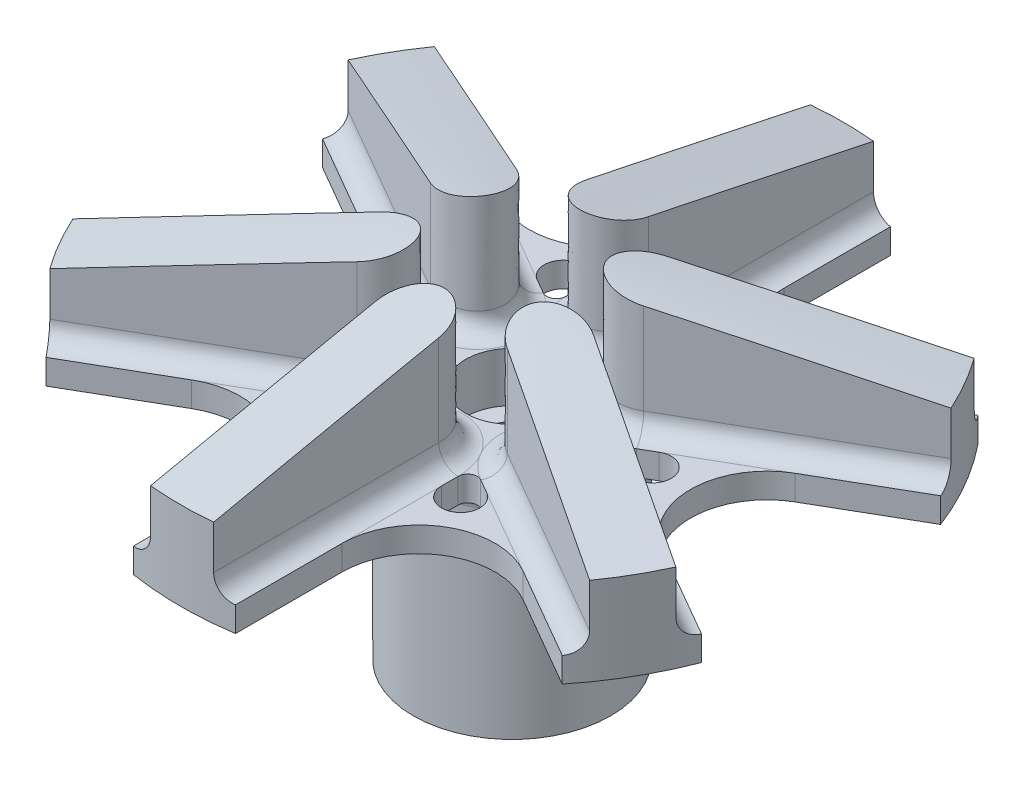
SolidWorks part; units mm, degrees
ref_plane "Front Plane" through (0, 0, 0) normal (0, 0, 1) x (1, 0, 0)
ref_plane "Top Plane" through (0, 0, 0) normal (0, 1, 0) x (1, 0, 0)
ref_plane "Right Plane" through (0, 0, 0) normal (1, 0, 0) x (0, 0, -1)
sketch "Sketch1" plane through (0, 0, 0) normal (0, 1, 0) x (1, 0, 0)
  circle A0 centre (0, 0) radius 26.67
  dimension "D1" = 53.34
extrude "impeller plate" add sketch "Sketch1" along normal blind 2
sketch "Sketch6" plane through (0, 0, 0) normal (0, -1, 0) x (-1, 0, 0)
  circle A0 centre (0, 0) radius 7.9375
  dimension "D1" = 15.875
extrude "boss" add sketch "Sketch6" along normal blind 17
sketch "Sketch7" plane through (0, -17, 0) normal (0, -1, 0) x (-1, 0, 0)
  circle A0 centre (0, 0) radius 2.1828
  dimension "D1" = 4.3656
extrude "bolt bore" cut sketch "Sketch7" against normal through all
sketch "Sketch8" plane through (0, -17, 0) normal (0, -1, 0) x (-1, 0, 0)
  circle A0 centre (0, 0) radius 4
  dimension "D1" = 8
extrude "shaft bore" cut sketch "Sketch8" against normal blind 12
sketch "Sketch9" plane through (0, 2, 0) normal (0, 1, 0) x (1, 0, 0)
  circle A0 centre (0, 0) radius 3.75
  dimension "D1" = 7.5
extrude "bolt head bore" cut sketch "Sketch9" against normal blind 4
sketch "Sketch11" plane through (0, -17, 0) normal (0, -1, 0) x (1, 0, 0)
  line L1 (-6, 1) -> (6, 1)
  line L2 (-6, 1) -> (-6, -1)
  line L3 (-6, -1) -> (6, -1)
  line L4 (6, 1) -> (6, -1)
  line L5 (-6, 1) -> (6, -1) construction
  line L6 (-6, -1) -> (6, 1) construction
  point P0 (0, 0)
  dimension "D1" = 12
  dimension "D2" = 2
extrude "dowel slot" cut sketch "Sketch11" against normal blind 3
sketch "Sketch12" plane through (0, 2, 0) normal (0, 1, 0) x (1, 0, 0)
  line L0 (0, 0) -> (26.67, 0) construction
  line L1 (5.2327, 1.5626) -> (26.6242, 1.5626)
  line L2 (5.2327, -1.5626) -> (26.6242, -1.5626)
  circle A0 centre (0, 0) radius 26.67 construction
  arc A3 (26.6242, -1.5626) -> (26.6242, 1.5626) centre (0, 0) ccw
  arc A4 (5.2327, -1.5626) -> (5.2327, 1.5626) centre (0, 0) ccw
  dimension "D3" = 10.922
  dimension "D1" = 1.5626
  dimension "D2" = 1.5626
extrude "opening alingment cut" cut sketch "Sketch12" against normal blind 1
pattern_circular "opening alingment pattern" count 6 over 360 about axis through (0, 2, 0) along (0, 1, 0) of "opening alingment cut"
sketch "Sketch14" plane through (0, 2, 0) normal (0, 1, 0) x (1, 0, 0)
  line L0 (0, 0) -> (26.67, 0) construction
  line L1 (26.6242, 1.5626) -> (5.2327, 1.5626) construction
  line L3 (24.2619, 11.0747) -> (8.5761, 2.0185) construction
  line L5 (0, 0) -> (23.0969, 13.335) construction
  line L7 (6.0361, 6.4179) -> (21.7219, 15.4741)
  line L9 (8.5761, 2.0185) -> (24.2619, 11.0747)
  arc A2 (26.6242, -1.5626) -> (26.6242, 1.5626) centre (0, 0) ccw construction
  arc A5 (26.6242, 1.5626) -> (14.6654, 22.2759) centre (0, 0) ccw construction
  circle A6 centre (0, 0) radius 5.461 construction
  circle A7 centre (0, 0) radius 5.461 construction
  arc A8 (24.2619, 11.0747) -> (21.7219, 15.4741) centre (0, 0) ccw
  ellipse E0 centre (7.3061, 4.2182) end of major axis (4.7294, 2.7305) minor radius 2.54 (6.0361, 6.4179) -> (8.5761, 2.0185) ccw
  dimension "D1" = 30
  dimension "D2" = 5.08
extrude "one blade" add sketch "Sketch14" along normal blind 9.5881
sketch "Sketch15" plane through (0, 2, 0) normal (0, 1, 0) x (1, 0, 0)
  circle A0 centre (0, 0) radius 26.67
  arc A1 (-26.6242, -1.5626) -> (-14.6654, -22.2759) centre (0, 0) ccw construction
  circle A2 centre (0, 0) radius 3.75
  circle A3 centre (0, 0) radius 3.75 construction
extrude "opening alignment fill" add sketch "Sketch15" against normal blind 2
pattern_circular "CirPattern2" count 6 over 360 about axis through (0, 2, 0) along (0, 1, 0) of "one blade"
sketch "Sketch16" plane through (0, 0, 0) normal (1, 0, 0) x (0, 0, -1)
  line L0 (0, 0) -> (0, 11.5881) construction
  line L2 (26.67, 0) -> (26.67, 7.08) construction
  line L3 (0, 11.5881) -> (5.461, 11.5881) construction
  line L4 (5.461, 11.5881) -> (26.67, 7.08)
  line L5 (26.67, 7.08) -> (26.67, 11.5881)
  line L6 (26.67, 11.5881) -> (5.461, 11.5881)
  line L7 (-26.67, 0) -> (26.67, 0) construction
  dimension "D1" = 7.08
  dimension "D2" = 5.461
  dimension "D3" = 26.67
  dimension "D4" = 11.5881
revolve "angle cut" cut sketch "Sketch16" angle 360 about L0
fillet "Fillet1" radius 1.5626 18 edges at (-16.419, 2, -6.5466) (-4.7294, 2, -2.7305) (-2.54, 2, -17.4926) (0, 2, -5.461) (16.419, 2, -6.5466) (4.7294, 2, -2.7305) (13.879, 2, 10.946) (4.7294, 2, 2.7305) (-13.879, 2, 10.946) (-16.419, 2, 6.5466) (-2.54, 2, 17.4926) (0, 2, 5.461) (-13.879, 2, -10.946) (2.54, 2, -17.4926) (13.879, 2, -10.946) (16.419, 2, 6.5466) (-4.7294, 2, 2.7305) (2.54, 2, 17.4926)
sketch "Sketch18" plane through (0, 2, 0) normal (0, 1, 0) x (1, 0, 0)
  line L0 (-20.7707, -16.7293) -> (-13.335, -12.4363)
  line L1 (4.1026, -26.3526) -> (4.1026, -17.7666)
  line L2 (4.1026, -8.4364) -> (4.1026, -26.3526) construction
  line L3 (20.7707, -16.7293) -> (13.335, -12.4363)
  line L4 (20.7707, -16.7293) -> (5.2548, -7.7712) construction
  line L5 (-4.1026, -26.3526) -> (-4.1026, -17.7666)
  line L6 (-24.8733, 9.6233) -> (-17.4376, 5.3303)
  line L7 (-24.8733, -9.6233) -> (-17.4376, -5.3303)
  line L8 (-4.1026, 26.3526) -> (-4.1026, 17.7666)
  line L9 (-20.7707, 16.7293) -> (-13.335, 12.4363)
  line L10 (20.7707, 16.7293) -> (13.335, 12.4363)
  line L11 (4.1026, 26.3526) -> (4.1026, 17.7666)
  line L12 (24.8733, -9.6233) -> (17.4376, -5.3303)
  line L13 (24.8733, 9.6233) -> (17.4376, 5.3303)
  line L14 (5.6414, -9.7711) -> (7.1801, -12.4363) construction
  line L15 (5.2548, -7.7712) -> (6.4107, -8.4386)
  line L16 (4.1026, -8.4364) -> (4.1026, -9.7711)
  line L17 (-4.1026, -8.4364) -> (-4.1026, -9.7711)
  line L18 (-5.2548, -7.7712) -> (-6.4107, -8.4386)
  line L19 (-9.3575, -0.6652) -> (-10.5134, -1.3326)
  line L20 (-9.3575, 0.6652) -> (-10.5134, 1.3326)
  line L21 (-5.2548, 7.7712) -> (-6.4107, 8.4386)
  line L22 (-4.1026, 8.4364) -> (-4.1026, 9.7711)
  line L23 (4.1026, 8.4364) -> (4.1026, 9.7711)
  line L24 (5.2548, 7.7712) -> (6.4107, 8.4386)
  line L25 (9.3575, 0.6652) -> (10.5134, 1.3326)
  line L26 (9.3575, -0.6652) -> (10.5134, -1.3326)
  arc A0 (4.1026, -17.7666) -> (13.335, -12.4363) centre (10.2575, -17.7666) cw
  arc A1 (4.1026, -26.3526) -> (20.7707, -16.7293) centre (0, 0) ccw
  circle A2 centre (10.2575, -17.7666) radius 6.1549 construction
  arc A3 (-20.7707, -16.7293) -> (-4.1026, -26.3526) centre (0, 0) ccw
  arc A4 (-13.335, -12.4363) -> (-4.1026, -17.7666) centre (-10.2575, -17.7666) cw
  arc A5 (-24.8733, 9.6233) -> (-24.8733, -9.6233) centre (0, 0) ccw
  arc A6 (-17.4376, 5.3303) -> (-17.4376, -5.3303) centre (-20.5151, 0) cw
  arc A7 (-4.1026, 26.3526) -> (-20.7707, 16.7293) centre (0, 0) ccw
  arc A8 (-4.1026, 17.7666) -> (-13.335, 12.4363) centre (-10.2575, 17.7666) cw
  arc A9 (20.7707, 16.7293) -> (4.1026, 26.3526) centre (0, 0) ccw
  arc A10 (13.335, 12.4363) -> (4.1026, 17.7666) centre (10.2575, 17.7666) cw
  arc A11 (24.8733, -9.6233) -> (24.8733, 9.6233) centre (0, 0) ccw
  arc A12 (17.4376, -5.3303) -> (17.4376, 5.3303) centre (20.5151, 0) cw
  arc A13 (4.1026, -9.7711) -> (6.4107, -8.4386) centre (5.6414, -9.7711) ccw
  arc A14 (5.2548, -7.7712) -> (4.1026, -8.4364) centre (4.8708, -8.4364) ccw
  arc A15 (-6.4107, -8.4386) -> (-4.1026, -9.7711) centre (-5.6414, -9.7711) ccw
  arc A16 (-4.1026, -8.4364) -> (-5.2548, -7.7712) centre (-4.8708, -8.4364) ccw
  arc A17 (-10.5134, 1.3326) -> (-10.5134, -1.3326) centre (-11.2827, 0) ccw
  arc A18 (-9.3575, -0.6652) -> (-9.3575, 0.6652) centre (-9.7415, 0) ccw
  arc A19 (-4.1026, 9.7711) -> (-6.4107, 8.4386) centre (-5.6414, 9.7711) ccw
  arc A20 (-5.2548, 7.7712) -> (-4.1026, 8.4364) centre (-4.8708, 8.4364) ccw
  arc A21 (6.4107, 8.4386) -> (4.1026, 9.7711) centre (5.6414, 9.7711) ccw
  arc A22 (4.1026, 8.4364) -> (5.2548, 7.7712) centre (4.8708, 8.4364) ccw
  arc A23 (10.5134, -1.3326) -> (10.5134, 1.3326) centre (11.2827, 0) ccw
  arc A24 (9.3575, 0.6652) -> (9.3575, -0.6652) centre (9.7415, 0) ccw
  spline S0 degree 3 poles (5.2548, -7.7712) (4.8829, -7.5565) (4.54, -7.295) (3.9364, -6.6984) (3.6698, -6.3563) (3.4573, -5.9882) knots 0 0 0 0 0.5 0.5 1 1 1 1 construction
  spline S1 degree 3 poles (3.4573, -5.9882) (3.5634, -6.1719) (3.6568, -6.3628) (3.8185, -6.7587) (3.8868, -6.9643) (4.0486, -7.5836) (4.1026, -8.0054) (4.1026, -8.4364) knots 0 0 0 0 0.25 0.25 0.5 0.5 1 1 1 1 construction
  point P16 (6.4107, -11.1037)
  point P85 (0, 0)
  dimension "D1" = 6
extrude "Cut-Extrude1" cut sketch "Sketch18" against normal through all
fillet "Fillet3" radius 1.016 1 edges at (0, 0, 7.9375)
equation "\"z\" = 6\t\t\t'number of blades"
equation "\"de_length\" = 10mm\t\t'entrance eye consistent length"
equation "\"av\" = \"ae\"*\"av_ratio\"\t\t'area between just two blades"
equation "\"d2\" = 2.1in \t\t\t'outer diameter of the impeller"
equation "\"theta\" = 12\t\t\t'angle of blades from inner to outer "
equation "\"b2\" = .2in\t\t\t'tip height from disc surface at d2; slightly higher than d_exit"
equation "\"b1\" = \"b2\" + (\"d2\"/2 - \"de\"/2)*tan(\"theta\") \t\t\t'tip height from disc surface at inlet eye"
equation "\"impeller base thickness\"= 2mm"
equation "\"impeller dowel diameter\" = 2mm"
equation "\"impeller bolt head diameter\" = \"m4 head bore diameter\""
equation "\"impeller bolt head depth\" = 4mm"
equation "\"impeller bolt stop depth\" = 3mm"
equation "\"impeller bolt bore\" = \"m4 clearance\""
equation "\"impeller shaft bore depth\" = 12mm"
equation "\"impeller shaft bore\" = 8mm"
equation "\"impeller boss depth\" = \"impeller shaft bore depth\"+\"impeller bolt stop depth\"+\"impeller bolt head depth\"-\"impeller base thickness\""
equation "\"impeller boss diameter\" = \"upper seal ID\""
equation "\"impeller dowel length\" = 2mm*2 + \"impeller shaft bore\""
equation "\"D1@Sketch1\"=\"d2\""
equation "\"D1@impeller plate\" = \"impeller base thickness\""
equation "\"D1@Sketch6\"=\"impeller boss diameter\""
equation "\"D1@boss\" = \"impeller boss depth\""
equation "\"D1@Sketch7\"=\"impeller bolt bore\""
equation "\"D1@Sketch8\"= \"impeller shaft bore\""
equation "\"D1@shaft bore\" = \"impeller shaft bore depth\""
equation "\"D1@Sketch9\"=\"impeller bolt head diameter\""
equation "\"D1@bolt head bore\" = \"impeller bolt head depth\""
equation "\"D1@Sketch11\"=\"impeller dowel length\""
equation "\"D2@Sketch11\"=\"impeller dowel diameter\""
equation "\"D1@dowel slot\" = \"impeller dowel diameter\" + 1mm"
equation "\"ae\" = 3.14*(\"de\"^2)/4\t\t'entrance eye area'"
equation "\"av_ratio\" = .32\t\t'ratio of av/ae at N_s of 470, range is .275 to .375, .325 ideal. High ratio means bigger area means smaller blades"
equation "\"s_open\" = \"av\"/\"b1\"\t\t'width of open area"
equation "\"de\" = 0.43in\t\t\t'entrance eye diameter"
equation "\"ce\" = 3.14*\"de\"\t\t'entrance eye circumference"
equation "\"D1@Sketch12\"=\"s_open\"/2"
equation "\"D3@Sketch12\"=\"de\""
equation "\"D1@opening alingment pattern\" = \"z\""
equation "\"D2@Sketch12\"=\"s_open\"/2"
equation "\"D1@one blade\" = \"b1\""
equation "\"D1@opening alignment fill\" = \"impeller base thickness\""
equation "\"D1@CirPattern2\"=\"z\""
equation "\"D1@Sketch16\"=\"impeller base thickness\"+\"b2\""
equation "\"D2@Sketch16\"=\"de\"/2"
equation "\"D3@Sketch16\"=\"d2\"/2"
equation "\"D1@Sketch14\"=360/\"z\"/2"
equation "\"D4@Sketch16\"=\"b1\"+\"impeller base thickness\""
equation "\"s\"=\"ce\" - \"z\"*\"s_open\""
equation "\"upper seal ID\"= 0.625in"
equation "\"m4 clearance\" = 0.171875in \t'this is 11/64 bit for 4.36mm"
equation "\"m4 tap\" = 0.125in\t\t'this is 1/8 bit for 3.17mm"
equation "\"m4 head bore diameter\" = 7.5mm"
equation "\"m4 head bore depth\" = 5mm\t'actual is ~4mm"
equation "\"d_exit\" = 0.18in \t\t'throat aka d1"
equation "\"bearing OD\" = 30mm"
equation "\"bearing ID\"= 10mm"
equation "\"bearing depth\"= 9mm"
equation "\"bearing outer race thickness\"= 1mm"
equation "\"bearing inner race thickness\"= 1mm"
equation "\"bearing bore\" = \"bearing depth\" + 1mm"
equation "\"lower seal OD\" = .917in\t\t'this is https://www.mcmaster.com/#9281k121/=174001b"
equation "\"lower seal ID\"= .375in"
equation "\"lower seal depth\" = .625in + .218in"
equation "\"lower seal bore\" = \"lower seal depth\" + 1mm"
equation "\"upper seal OD\" = 1.125in\t'this is https://www.mcmaster.com/#5154t33/=173zuau, needs to be visually inspected before machining!"
equation "\"upper seal depth\"= .25in\t'aka height; these values need to be confirmed by inspection!! We may want to compress the height."
equation "\"upper seal bore\" = \"upper seal depth\" + 1mm"
equation "\"big o-ring thickness\" = .139in"
equation "\"big o-ring OD\" = 2.734in"
equation "\"big o-ring ID\" = 3.012in"
equation "\"big o-ring groove depth\" = \"big o-ring thickness\"*4/5"
equation "\"impeller center height\" = \"impeller base thickness\" + \"b1\"\t'impeller height at de"
equation "\"impeller outer height\" = \"impeller base thickness\" + \"b2\"\t'impeller height at de"
equation "\"impeller upper clearance\"= .5mm"
equation "\"impeller horizontal clearance\"= (\"d2\"*1.15 - \"d2\")/2 \t\t'clearance based on D2-D3 ratio for circular volute, ranges 1.15 to 1.2"
equation "\"impeller bottom clearance\"= .5mm"
equation "\"coupler motor shaft hole ID\"= 8mm"
equation "\"coupler OD\"= 17mm"
equation "\"coupler length\"= 25mm"
equation "\"motor OD\" = 64mm"
equation "\"motor shaft diameter\"= 8mm"
equation "\"motor shaft pride\"= 32mm"
equation "\"motor to bearing plate distance\" = \"motor shaft pride\" + 2mm +\"coupler length\"/2"
equation "\"square plate bolt bore\" = 8mm"
equation "\"square plate bolt head diameter\" = 13.5mm"
equation "\"square plate bolt head depth\" = 8mm"
equation "\"square plate bolt pattern diameter\"= 3.5in"
equation "\"motor mount center bore\"= \"coupler OD\"+ 4mm"
equation "\"motor mount post radius\"= ( 3 * \"square plate bolt bore\" ) / 2"
equation "\"motor mount m4 screw hole diameter\"= 4mm"
equation "\"motor mount m4 head diameter\"= 7.25mm"
equation "\"motor mount m4 head depth\"= 4mm"
equation "\"motor mount m4 pattern diamater\" = 30mm"
equation "\"motor mount plate thickness\"= 8mm + \"motor mount m4 head depth\""
equation "\"bearing plate stop ID\" = \"bearing OD\" - 4mm"
equation "\"bearing plate stop depth\" = 3mm"
equation "\"lower seal plate lip depth\" = 2mm"
equation "\"lower seal plate lip ID\" = \"lower seal OD\" - 3mm"
equation "\"lower seal plate thickness\" = \"lower seal plate lip depth\" + \"lower seal bore\""
equation "\"shaft coupler section diameter\" = 8mm"
equation "\"shaft coupler section length\" = \"motor to bearing plate distance\" - \"motor shaft pride\" - 2mm"
equation "\"shaft bearing section diameter\" = \"bearing ID\""
equation "\"shaft bearing section length\" = \"bearing plate stop depth\" + \"bearing depth\""
equation "\"shaft bearing stop diameter\" = \"bearing ID\" + 4mm"
equation "\"shaft bearing stop length\" = 3mm"
equation "\"shaft lower seal section diameter\" = \"lower seal ID\""
equation "\"shaft lower seal section length\" = \"lower seal plate thickness\" + 1mm"
equation "\"shaft impeller section diameter\" = \"impeller shaft bore\""
equation "\"upper seal plate lip ID\" = \"upper seal OD\" - 3mm"
equation "\"upper seal plate pressure hole diameter\" = .125in\t'this is 1/8 drill "
equation "\"upper seal plate pressure tap diameter\" = .328125in \t'this is 21/64 drill for a 1/8 ANPT tap"
equation "\"upper seal plate pressure tap grip\" = 4mm\t\t'this is the area around the tap so it doesn't crack"
equation "\"upper seal plate pressure tap depth\" = 12"
equation "\"impeller cavity center height\"= \"impeller bottom clearance\" + \"impeller upper clearance\" + \"impeller center height\""
equation "\"impeller cavity diameter\"= 2 * \"impeller horizontal clearance\" + \"d2\" \t\t\t\t\t\t\t\t\t'called D3 analytically"
equation "\"impeller cavity outer height\"= \"impeller bottom clearance\" + \"impeller upper clearance\" + \"impeller base thickness\" + \"b2\" \t\t'this is height at impeller diameter d2, not at d3"
equation "\"impeller housing diameter\" = \"square plate bolt pattern diameter\" + 2*\"motor mount post radius\""
equation "\"impeller housing bolt count\" = 8"
equation "\"impeller housing bolt pattern diameter\" = 3.5in"
equation "\"impeller housing threaded inlet diameter\" = 0.6875in \t\t'this is the 11/16 drill size for 1/2 npt fitting"
equation "\"impeller housing threaded inlet depth\"= 15mm"
equation "\"impeller housing exit threaded diameter\"= 0.6875in \t\t'this is the 11/16 drill size for 1/2 npt fitting"
equation "\"impeller housing exit threaded depth\"= 18mm"
equation "\"impeller housing diffuser conical angle\"=10"
equation "\"impeller housing diffuser tangent angle\"=5"
equation "\"impeller housing diffuser final diameter\" = .5in"
equation "\"impeller housing outlet grip\" = 5mm"
equation "\"end mill size\" = 0.375in\t'for 3/8 endmill"
equation "\"m6 clearance\" = 0.234375in\t'this is 15/64 bit = 5.95mm, could use 6mm bit, B bit for 6.04mm or 1/4 bit for 6.35mm"
equation "\"m6 tap\" = 5mm\t\t\t'5mm is appropriate, could use 13/64 or #5,6,7"
equation "\"m6 head bore diameter\" = 11mm\t\t"
equation "\"m6 head bore depth\" = 7mm\t'actual is 6mm"
equation "\"m8 clearance\" = 0.3125in\t'this is 5/16in for 7.93mm, could use 8mm, O,P, or 21/64"
equation "\"m8 tap\" = 0.265625in\t\t'this is 17/64 for 6.746875mm"
equation "\"m8 head bore diameter\" = 14mm"
equation "\"min blade thickness\" = .2in"
equation "\"bearing plate thickness\" = \"bearing bore\" + \"bearing plate stop depth\" + \"shaft bearing stop length\""
equation "\"shaft impeller section length\" = \"upper seal plate thickness\" + \"upper seal plate riser\" + \"impeller bottom clearance\" + \"impeller base thickness\" - \"impeller bolt head depth\" - \"impeller bolt stop depth\""
equation "\"upper seal plate thickness\" = \"upper seal plate pressure hole diameter\"*3"
equation "\"upper seal plate riser\" = \"impeller housing thickness\"/2 - \"b2\"/2 - \"impeller base thickness\" - \t\"impeller bottom clearance\"\t\t\t'this offsets the gap under the housing"
equation "\"impeller housing thickness\"= \"impeller housing exit threaded diameter\" + 2*\"impeller housing outlet grip\""
equation "\"impeller housing bolt diameter\" = \"m6 clearance\""
equation "\"m8 head bore depth\"= 9mm\t'actual is 8mm"
equation "\"D2@Sketch14\"=\"min blade thickness\""
equation "\"D1@Fillet1\"=\"s_open\"/2"
